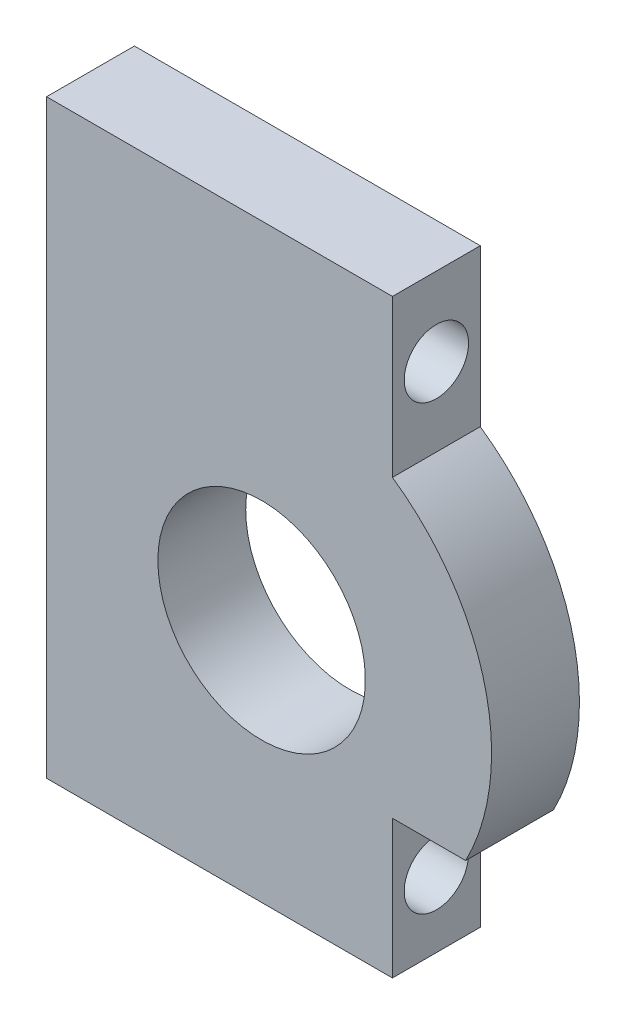
SolidWorks part; units mm, degrees
material "1060 Alloy"
ref_plane "Front Plane" through (0, 0, 0) normal (0, 0, 1) x (1, 0, 0)
ref_plane "Top Plane" through (0, 0, 0) normal (0, 1, 0) x (1, 0, 0)
ref_plane "Right Plane" through (0, 0, 0) normal (1, 0, 0) x (0, 0, -1)
sketch "Sketch2" plane through (0, 0, -13.2) normal (0, 0, -1) x (-1, 0, 0)
  line L0 (-19.1, 36.72) -> (-44.1, 36.72) construction
  line L1 (-44.1, 36.72) -> (-44.1, 46.72) construction
  line L2 (-19.1, 36.72) -> (-19.1, 79.385) construction
  line L3 (-19.1, 79.385) -> (-44.1, 79.385) construction
  line L4 (-44.1, 79.385) -> (-44.1, 68.055) construction
  line L5 (-44.1, 46.72) -> (-49.3933, 46.72) construction
  line L6 (-19.1, 36.72) -> (-44.1, 36.72)
  line L7 (-44.1, 36.72) -> (-44.1, 46.72)
  line L8 (-19.1, 36.72) -> (-19.1, 79.385)
  line L9 (-19.1, 79.385) -> (-44.1, 79.385)
  line L10 (-44.1, 79.385) -> (-44.1, 68.055)
  line L11 (-44.1, 46.72) -> (-49.3933, 46.72)
  arc A0 (-44.1, 68.055) -> (-49.3933, 46.72) centre (-34.645, 54.385) ccw construction
  arc A1 (-44.1, 68.055) -> (-49.3933, 46.72) centre (-34.645, 54.385) ccw
  circle A2 centre (-34.645, 54.385) radius 7.5
  circle A3 centre (-34.645, 54.385) radius 7.5 construction
  circle A4 centre (-34.645, 54.385) radius 5 construction
  dimension "D1" = 10
extrude "Boss-Extrude1" add sketch "Sketch2" along normal blind 3.175 and the other way blind 3.175
sketch "Sketch3" plane through (44.1, 0, 0) normal (1, 0, 0) x (0, 0, -1)
  line L0 (13.2, 41.72) -> (0, 41.72) construction
  line L1 (13.2, 41.72) -> (13.2, 73.72) construction
  line L2 (16.375, 46.72) -> (16.375, 36.72) construction
  line L3 (10.025, 46.72) -> (10.025, 36.72) construction
  line L4 (0, 39.395) -> (13.2, 39.395) construction
  line L5 (13.2, 73.72) -> (0, 73.72) construction
  circle A0 centre (13.2, 41.72) radius 2.325
  circle A1 centre (13.2, 73.72) radius 2.325
extrude "Cut-Extrude1" cut sketch "Sketch3" against normal up to next
